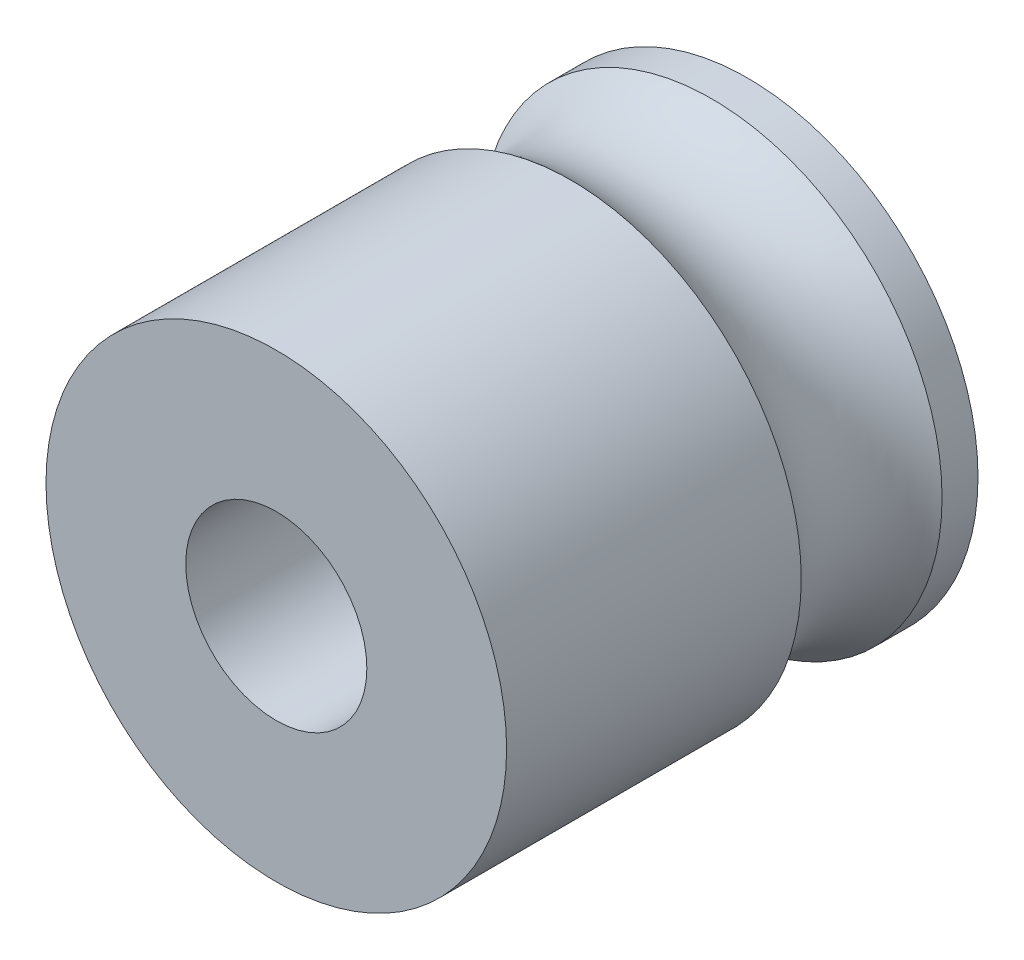
SolidWorks part; units mm, degrees
ref_plane "Front Plane" through (0, 0, 0) normal (0, 0, 1) x (1, 0, 0)
ref_plane "Top Plane" through (0, 0, 0) normal (0, 1, 0) x (1, 0, 0)
ref_plane "Right Plane" through (0, 0, 0) normal (1, 0, 0) x (0, 0, -1)
sketch "Sketch1" plane through (0, 0, 0) normal (0, 1, 0) x (1, 0, 0)
  line L0 (0, 0) -> (0, -8.2) construction
  line L1 (0, -8.2) -> (-2.52, -8.2) construction
  line L2 (0, 0) -> (-6.41, 0) construction
  line L3 (-2.52, -8.2) -> (-2.52, 4.92)
  line L4 (-2.52, 4.92) -> (-6.41, 4.92)
  line L5 (-2.52, -8.2) -> (-6.41, -8.2)
  line L6 (-6.41, 4.92) -> (-6.41, 3.92)
  line L7 (-6.41, -8.2) -> (-6.41, 0)
  line L8 (-6.41, 3.92) -> (-6.41, 0) construction
  line L9 (-2.52, 1.96) -> (0, 1.96) construction
  line L10 (0, 1.96) -> (-6.41, 1.96) construction
  arc A0 (-6.41, 3.92) -> (-6.41, 0) centre (-8.6194, 1.96) cw
  dimension "D1" = 2.9535
  dimension "D2" = 2.52
  dimension "D3" = 6.41
  dimension "D4" = 8.6194
  dimension "D5" = 4.92
  dimension "D6" = 8.2
revolve "Revolve1" add sketch "Sketch1" angle 360 about L0
